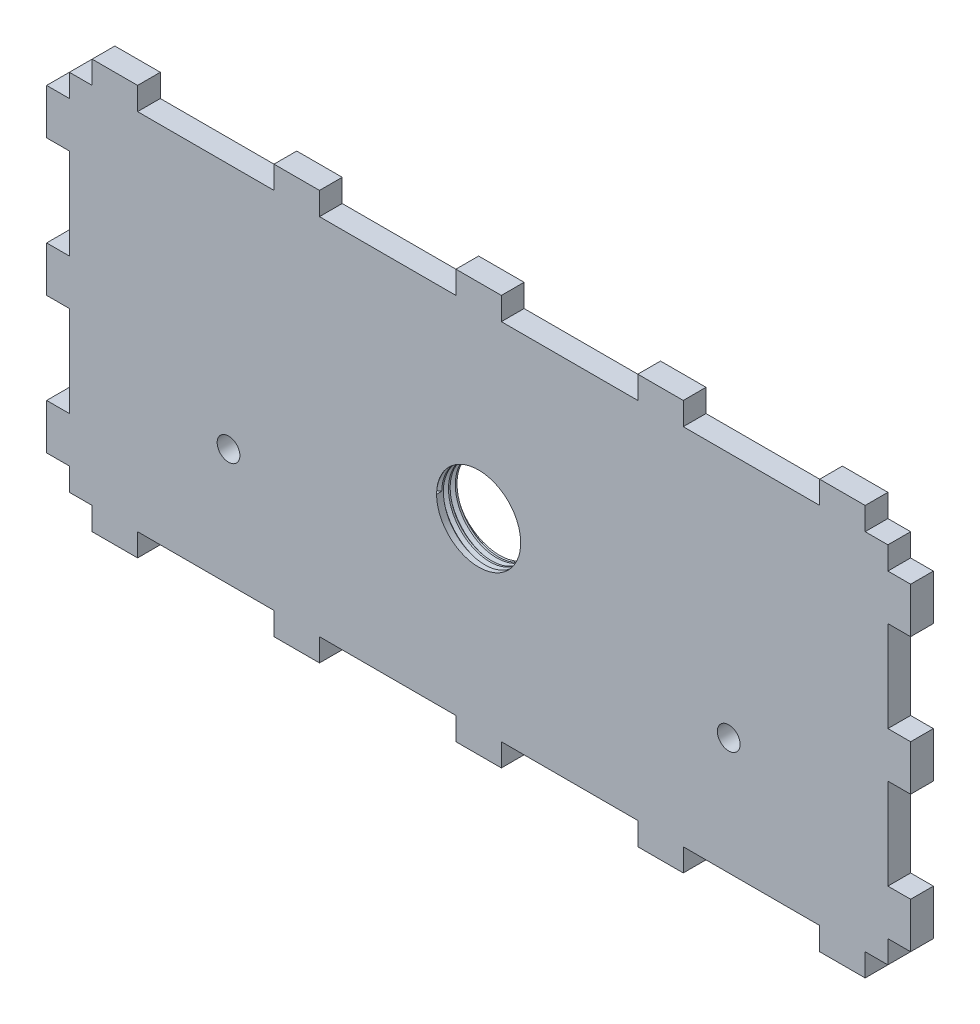
SolidWorks part; units mm, degrees
ref_plane "Ön Düzlem" through (0, 0, 0) normal (0, 0, 1) x (1, 0, 0)
ref_plane "Üst Düzlem" through (0, 0, 0) normal (0, 1, 0) x (1, 0, 0)
ref_plane "Sağ Düzlem" through (0, 0, 0) normal (1, 0, 0) x (0, 0, -1)
sketch "Sketch1" plane through (0, 0, 0) normal (0, 0, 1) x (1, 0, 0)
  line L0 (-85, 40) -> (-85, 45)
  line L1 (-90, -40) -> (-85, -40)
  line L2 (-90, -40) -> (-90, -35)
  line L3 (-90, 40) -> (-85, 40)
  line L4 (90, -40) -> (90, -35)
  line L5 (-90, -40) -> (90, 40) construction
  line L6 (-90, 40) -> (90, -40) construction
  line L7 (-85, 45) -> (-75, 45)
  line L8 (-75, 45) -> (-75, 40)
  line L9 (-45, 40) -> (-45, 45)
  line L10 (-35, 45) -> (-35, 40)
  line L11 (-45, 45) -> (-35, 45)
  line L12 (-5, 40) -> (-5, 45)
  line L13 (5, 45) -> (5, 40)
  line L14 (-5, 45) -> (5, 45)
  line L15 (35, 40) -> (35, 45)
  line L16 (45, 45) -> (45, 40)
  line L17 (35, 45) -> (45, 45)
  line L18 (75, 40) -> (75, 45)
  line L19 (85, 45) -> (85, 40)
  line L20 (75, 45) -> (85, 45)
  line L21 (-75, 40) -> (-45, 40)
  line L22 (-35, 40) -> (-5, 40)
  line L23 (5, 40) -> (35, 40)
  line L24 (45, 40) -> (75, 40)
  line L25 (85, 40) -> (90, 40)
  line L26 (-95, 0) -> (95, 0) construction
  line L27 (0, -40) -> (0, 40) construction
  line L28 (-90, 35) -> (-95, 35)
  line L29 (-95, 35) -> (-95, 25)
  line L30 (-95, 25) -> (-90, 25)
  line L31 (-95, -5) -> (-90, -5)
  line L32 (-90, 5) -> (-95, 5)
  line L33 (-95, 5) -> (-95, -5)
  line L34 (-95, -35) -> (-90, -35)
  line L35 (-90, -25) -> (-95, -25)
  line L36 (-95, -25) -> (-95, -35)
  line L37 (95, 25) -> (90, 25)
  line L38 (90, 35) -> (95, 35)
  line L39 (95, 35) -> (95, 25)
  line L40 (90, 5) -> (95, 5)
  line L41 (95, 5) -> (95, -5)
  line L42 (95, -5) -> (90, -5)
  line L43 (90, -25) -> (95, -25)
  line L44 (95, -25) -> (95, -35)
  line L45 (95, -35) -> (90, -35)
  line L46 (85, -45) -> (85, -40)
  line L47 (75, -45) -> (85, -45)
  line L48 (75, -40) -> (75, -45)
  line L49 (45, -45) -> (45, -40)
  line L50 (35, -45) -> (45, -45)
  line L51 (35, -40) -> (35, -45)
  line L52 (5, -45) -> (5, -40)
  line L53 (-5, -45) -> (5, -45)
  line L55 (-35, -45) -> (-35, -40)
  line L56 (-45, -45) -> (-35, -45)
  line L57 (-45, -40) -> (-45, -45)
  line L58 (-75, -45) -> (-75, -40)
  line L59 (-85, -45) -> (-75, -45)
  line L60 (-85, -40) -> (-85, -45)
  line L61 (-75, -40) -> (-45, -40)
  line L63 (5, -40) -> (35, -40)
  line L64 (45, -40) -> (75, -40)
  line L65 (85, -40) -> (90, -40)
  line L66 (-90, -25) -> (-90, -5)
  line L67 (-90, 5) -> (-90, 25)
  line L68 (-90, 35) -> (-90, 40)
  line L69 (90, 35) -> (90, 40)
  line L70 (90, 5) -> (90, 25)
  line L71 (90, -25) -> (90, -5)
  line L72 (-35, -40) -> (-5, -40)
  line L73 (-5, -40) -> (-5, -45)
  line L74 (-65.1041, -14.2699) -> (55.0196, -14.2699) construction
  circle A4 centre (0, 0) radius 9.25
  circle A5 centre (-55, -14.2699) radius 2.5
  circle A6 centre (55, -14.2699) radius 2.5
  point P0 (0, 0)
  point P82 (54.8959, -14.2699)
  point P83 (-65.1041, -14.2699)
  dimension "D3" = 18.5
  dimension "D5" = 110
  dimension "D4" = 5
  dimension "D1" = 80
  dimension "D2" = 180
  dimension "D7" = 10
  dimension "D8" = 5
  dimension "D9" = 5
  dimension "D11" = 30
  dimension "D12" = 5
  dimension "D13" = 10
  dimension "D14" = 5
  dimension "D16" = 30
  dimension "D17" = 20
  dimension "D18" = 30
  dimension "D10" = 5
  dimension "D15" = 3
extrude "Boss-Extrude1" add sketch "Sketch1" along normal blind 5
thread "Thread1" pitch 1.5 method cut profile "Thread Profile1" start angle 0, offset 0, length 0, pitch 1.5, diameter 18.5
ref_plane "Plane1" through (-9.25, 0, 5) normal (0, -1, 0) x (-1, 0, 0)
sketch "Thread Profile1" plane through (-9.25, 0, 5) normal (0, -1, 0) x (-1, 0, 0)
  line L0 (0, 0) -> (0, 1.5) construction
  line L1 (0, 0) -> (0.8119, 0.4687)
  line L2 (0.8119, 0.4687) -> (0.8119, 0.6562)
  line L3 (0.8119, 0.6562) -> (0, 1.125)
  line L4 (0.8119, 0.5625) -> (0, 0.5625) construction
  line L11 (0, 0) -> (0, 1.125)
  point P2 (0, 0)
  dimension "Pitch" = 1.5
  dimension "Profile_Angle" = 60
  dimension "Profile_Land" = 0.1875
  dimension "Profile_Height" = 0.8119
